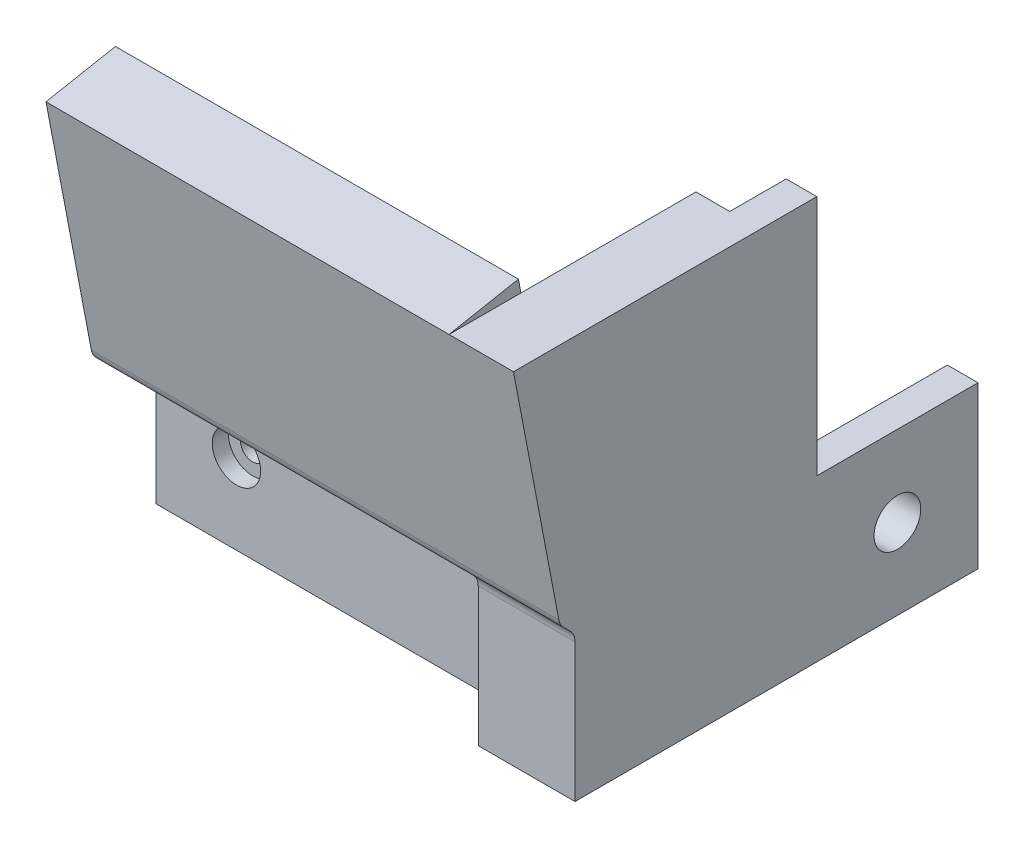
SolidWorks part; units mm, degrees
ref_plane "前视基准面" through (0, 0, 0) normal (0, 0, 1) x (1, 0, 0)
ref_plane "上视基准面" through (0, 0, 0) normal (0, 1, 0) x (1, 0, 0)
ref_plane "右视基准面" through (0, 0, 0) normal (1, 0, 0) x (0, 0, -1)
other "Configuration Table"
sketch "草图1" plane through (0, 0, 0) normal (1, 0, 0) x (0, 0, -1)
  line L0 (0, 0) -> (-10, 0)
  line L1 (-10, 0) -> (-17.6299, 40)
  line L2 (-17.6299, 40) -> (-10, 41.4554)
  line L3 (-10, 41.4554) -> (-4, 10)
  line L4 (-4, 10) -> (0, 10)
  line L5 (0, 10) -> (0, 0)
  dimension "D1" = 10
  dimension "D2" = 4
  dimension "D3" = 10
  dimension "D4" = 6
  dimension "D5" = 40
extrude "凸台-拉伸1" add sketch "草图1" along normal blind 50
sketch "草图2" plane through (0, 0, 0) normal (0, -1, 0) x (1, 0, 0)
  line L4 (0, 10) -> (0, 0)
  line L5 (0, 0) -> (50, 0)
  line L6 (50, 0) -> (50, 10)
  line L7 (50, 10) -> (0, 10)
  line L8 (0, 10) -> (0, 0)
  line L9 (0, 0) -> (50, 0)
  line L10 (50, 0) -> (50, 10)
  line L11 (50, 10) -> (0, 10)
  dimension "D1" = 0
extrude "凸台-拉伸2" add sketch "草图2" along normal blind 10
sketch "草图3" plane through (0, 0, 0) normal (-1, 0, 0) x (0, 0, 1)
  line L1 (0, 10) -> (10, 10)
  line L2 (0, 10) -> (0, -10)
  line L3 (0, -10) -> (10, -10)
  line L4 (10, 10) -> (10, -10)
extrude "凸台-拉伸3" add sketch "草图3" along normal blind 20
sketch "草图4" plane through (0, 10, 0) normal (0, 1, 0) x (1, 0, 0)
  line L1 (-20, 0) -> (0, 0)
  line L2 (-20, 0) -> (-20, -10)
  line L3 (-20, -10) -> (0, -10)
  line L4 (0, 0) -> (0, -10)
extrude "凸台-拉伸4" add sketch "草图4" along normal blind 30
sketch "草图5" plane through (50, 0, 0) normal (1, 0, 0) x (0, 0, -1)
  line L0 (-10, 10.004) -> (-11.9082, 10.004)
  line L1 (-17.6299, 40) -> (-10, 0) construction
  line L2 (-11.9082, 10.004) -> (-10, 0)
  line L3 (-10, 0) -> (-10, 10.004)
extrude "切除-拉伸1" cut sketch "草图5" against normal up to surface (50 mm away) up to face at (0, 32.2911, 11.4705)
chamfer "倒角1" distance 2 angle 45 1 edges at (25, 10.004, 10)
sketch "草图9" plane through (0, 0, 10) normal (0, 0, 1) x (1, 0, 0)
  line L0 (-20, 40) -> (-10, 40) construction
  line L1 (-20, 40) -> (0, 40) construction
  line L2 (-10, 40) -> (-10, 20) construction
  line L3 (50, -10) -> (50, 0) construction
  line L4 (50, -10) -> (50, 8.004) construction
  line L5 (50, 0) -> (10, 0) construction
  line L6 (-20, -10) -> (-20, 40) construction
  circle A0 centre (-10, 20) radius 1.5
  circle A1 centre (10, 0) radius 1.5
  dimension "D3" = 3
  dimension "D5" = 3
  dimension "D4" = 30
  dimension "D1" = 10
  dimension "D2" = 20
extrude "切除-拉伸2" cut sketch "草图9" against normal through all
sketch "草图12" plane through (0, 0, 10) normal (0, 0, 1) x (1, 0, 0)
  line L8 (0, 40) -> (-20, 40)
  line L9 (50, -10) -> (50, 8.004)
  line L10 (50, 8.004) -> (0, 8.004)
  line L11 (0, 8.004) -> (0, 40)
  line L15 (50, -10) -> (50, 8.004)
  line L16 (50, 8.004) -> (0, 8.004)
  line L17 (0, 8.004) -> (0, 40)
  line L19 (0, 40) -> (-20, 40)
  line L20 (-20, 40) -> (-20, -10)
  line L21 (-20, 40) -> (-20, -10)
  line L22 (-20, -10) -> (50, -10)
  line L23 (-20, -10) -> (50, -10)
  dimension "D1" = 0
extrude "切除-拉伸4" cut sketch "草图12" against normal blind 6
sketch "草图13" plane through (0, 8.004, 0) normal (0, -1, 0) x (1, 0, 0)
  line L0 (50, 4) -> (0, 4) construction
  line L1 (0, 10) -> (4, 10)
  line L2 (0, 10) -> (0, 4)
  line L3 (0, 4) -> (4, 4)
  line L4 (4, 10) -> (4, 4)
  line L6 (50, 10) -> (46, 10)
  line L7 (50, 10) -> (50, 4)
  line L8 (50, 4) -> (46, 4)
  line L9 (46, 10) -> (46, 4)
  dimension "D1" = 4
  dimension "D2" = 4
extrude "凸台-拉伸12" add sketch "草图13" along normal up to surface (18.004 mm away) up to face at (15, -10, 2)
fillet "圆角2" radius 2 3 edges at (25, 9.8906, 11.8866) (48, 8.004, 10) (2, 8.004, 10)
sketch "草图15" plane through (0, 0, 0) normal (0, 0, -1) x (-1, 0, 0)
  line L0 (-25, 10) -> (-25, 20.01) construction
  line L1 (0, 40) -> (20, 40) construction
  line L2 (0, 40) -> (0, -10) construction
  line L3 (0, -10) -> (20, -10) construction
  line L4 (20, 40) -> (20, -10) construction
  line L5 (-50, 10) -> (0, 10) construction
  line L6 (-50, -10) -> (-70, -10)
  line L7 (-70, 40) -> (-70, -10)
  line L8 (-50, 40) -> (-70, 40)
  line L9 (-50, 40) -> (-50, -10)
  circle A0 centre (10, 20) radius 1.5 construction
  circle A1 centre (-60, 20) radius 1.5
extrude "凸台-拉伸14" add sketch "草图15" against normal up to surface (4 mm away) up to face at (-8.5, 20, 4)
sketch "草图16" plane through (0, 0, 4) normal (0, 0, 1) x (1, 0, 0)
  line L5 (-20, -10) -> (0, -10)
  line L6 (0, -10) -> (0, 10)
  line L7 (0, 10) -> (0, 40)
  line L8 (0, 40) -> (-20, 40)
  line L9 (-20, 40) -> (-20, -10)
  line L10 (-20, -10) -> (0, -10)
  line L11 (0, -10) -> (0, 10)
  line L12 (0, 10) -> (0, 40)
  line L13 (0, 40) -> (-20, 40)
  line L14 (-20, 40) -> (-20, -10)
  dimension "D1" = 0
extrude "切除-拉伸5" cut sketch "草图16" against normal up to surface (4 mm away) up to face at (-8.5, 20, 0)
sketch "草图17" plane through (0, 0, 4) normal (0, 0, 1) x (1, 0, 0)
  line L0 (70, -10) -> (50, -10) construction
  line L1 (70, 40) -> (54, 40)
  line L2 (70, 40) -> (70, -10)
  line L3 (70, -10) -> (54, -10)
  line L4 (54, 40) -> (54, -10)
  dimension "D1" = 16
extrude "切除-拉伸6" cut sketch "草图17" against normal up to surface (4 mm away) up to face at (11.5, 0, 0)
sketch "草图18" plane through (50, 0, 0) normal (-1, 0, 0) x (0, 0, 1)
  line L0 (0, 10) -> (4, 10)
  line L1 (4, 10) -> (5.9075, 20)
  line L2 (4, 10) -> (10, 41.4554) construction
  line L3 (5.9075, 20) -> (0, 20)
  line L4 (0, 10) -> (0, 40) construction
  line L5 (0, 20) -> (0, 10)
  dimension "D1" = 10
extrude "凸台-拉伸15" add sketch "草图18" along normal blind 10
sketch "草图20" plane through (0, 0, 0) normal (0, 0, -1) x (-1, 0, 0)
  line L1 (-50, 40) -> (-54, 40)
  line L2 (-50, 40) -> (-50, -10)
  line L3 (-50, -10) -> (-54, -10)
  line L4 (-54, 40) -> (-54, -10)
extrude "凸台-拉伸16" add sketch "草图20" along normal blind 20
sketch "草图23" plane through (54, 0, 0) normal (1, 0, 0) x (0, 0, -1)
  line L0 (-4, -10) -> (-4, 20) construction
  line L1 (-4, 12) -> (20, 12)
  line L2 (-4, 12) -> (-4, -10)
  line L3 (-4, -10) -> (20, -10)
  line L4 (20, 12) -> (20, -10)
  line L5 (-5.9075, 20) -> (-4, 20) construction
  dimension "D1" = 8
extrude "切除-拉伸9" cut sketch "草图23" against normal up to surface (4 mm away) up to face at (50, 13.7188, 9.5514)
sketch "草图24" plane through (0, 0, 4) normal (0, 0, 1) x (1, 0, 0)
  line L5 (50, 12) -> (54, 12)
  line L6 (54, 12) -> (54, 40)
  line L7 (54, 40) -> (50, 40)
  line L8 (50, 40) -> (50, 20)
  line L9 (50, 20) -> (50, 12)
  line L10 (50, 12) -> (54, 12)
  line L11 (54, 12) -> (54, 40)
  line L12 (54, 40) -> (50, 40)
  line L13 (50, 40) -> (50, 20)
  line L14 (50, 20) -> (50, 12)
  dimension "D1" = 0
extrude "凸台-拉伸17" add sketch "草图24" along normal up to surface (13.6299 mm away) up to face at (25, 25.2475, 14.8159)
sketch "草图25" plane through (0, 12, 0) normal (0, -1, 0) x (1, 0, 0)
  line L1 (50, 0) -> (54, 0)
  line L2 (50, 0) -> (50, 12.289)
  line L3 (50, 12.289) -> (54, 12.289)
  line L4 (54, 0) -> (54, 12.289)
extrude "凸台-拉伸18" add sketch "草图25" along normal up to surface (22 mm away) up to face at (25, -10, 6)
sketch "草图26" plane through (50, 0, 0) normal (-1, 0, 0) x (0, 0, 1)
  line L5 (12.289, -10) -> (12.289, 12)
  line L6 (12.289, 12) -> (12.0019, 10.495)
  line L7 (11.4515, 9.4555) -> (10.5858, 8.5898)
  line L8 (10, 7.1756) -> (10, -10)
  line L9 (10, -10) -> (12.289, -10)
  line L10 (12.289, -10) -> (12.289, 12)
  line L11 (12.289, 12) -> (12.0019, 10.495)
  line L12 (11.4515, 9.4555) -> (10.5858, 8.5898)
  line L13 (10, 7.1756) -> (10, -10)
  line L14 (10, -10) -> (12.289, -10)
  arc A2 (11.4515, 9.4555) -> (12.0019, 10.495) centre (10.0373, 10.8697) ccw
  arc A3 (10.5858, 8.5898) -> (10, 7.1756) centre (12, 7.1756) ccw
  arc A4 (11.4515, 9.4555) -> (12.0019, 10.495) centre (10.0373, 10.8697) ccw
  arc A5 (10.5858, 8.5898) -> (10, 7.1756) centre (12, 7.1756) ccw
  dimension "D1" = 0
extrude "切除-拉伸10" cut sketch "草图26" against normal up to surface (4 mm away) up to face at (54, 13.7143, 0.3154)
sketch "草图27" plane through (4, 0, 0) normal (1, 0, 0) x (0, 0, -1)
  line L5 (-10, -10) -> (-4, -10)
  line L6 (-4, -10) -> (-4, 8.004)
  line L7 (-4, 8.004) -> (-10, 8.004)
  line L8 (-10, 8.004) -> (-10.5858, 8.5898)
  line L9 (-10, 7.1756) -> (-10, -10)
  line L10 (-10, -10) -> (-4, -10)
  line L11 (-4, -10) -> (-4, 8.004)
  line L12 (-4, 8.004) -> (-10, 8.004)
  line L13 (-10, 8.004) -> (-10.5858, 8.5898)
  line L14 (-10, 7.1756) -> (-10, -10)
  arc A1 (-10, 7.1756) -> (-10.5858, 8.5898) centre (-12, 7.1756) ccw
  arc A2 (-10, 7.1756) -> (-10.5858, 8.5898) centre (-12, 7.1756) ccw
  dimension "D1" = 0
extrude "切除-拉伸11" cut sketch "草图27" against normal up to surface (4 mm away) up to face at (0, 11.7188, 8.5607)
sketch "草图31" plane through (40, 0, 0) normal (-1, 0, 0) x (0, 0, 1)
  line L4 (0, 20) -> (0, 10)
  line L5 (0, 10) -> (4, 10)
  line L6 (4, 10) -> (5.9075, 20)
  line L7 (5.9075, 20) -> (0, 20)
  line L8 (0, 20) -> (0, 10)
  line L9 (0, 10) -> (4, 10)
  line L10 (4, 10) -> (5.9075, 20)
  line L11 (5.9075, 20) -> (0, 20)
  dimension "D1" = 0
extrude "切除-拉伸14" cut sketch "草图31" against normal blind 10
sketch "草图32" plane through (54, 0, 0) normal (1, 0, 0) x (0, 0, -1)
  line L8 (-10, 7.1756) -> (-10, -10)
  line L9 (-10, -10) -> (0, -10)
  line L10 (0, -10) -> (0, 12)
  line L11 (0, 12) -> (20, 12)
  line L12 (20, 12) -> (20, 40)
  line L13 (20, 40) -> (-17.6299, 40)
  line L14 (-17.6299, 40) -> (-12.0019, 10.495)
  line L15 (-11.4515, 9.4555) -> (-10.5858, 8.5898)
  line L16 (-10, 7.1756) -> (-10, -10)
  line L17 (-10, -10) -> (0, -10)
  line L18 (0, -10) -> (0, 12)
  line L19 (0, 12) -> (20, 12)
  line L20 (20, 12) -> (20, 40)
  line L21 (20, 40) -> (-17.6299, 40)
  line L22 (-17.6299, 40) -> (-12.0019, 10.495)
  line L23 (-11.4515, 9.4555) -> (-10.5858, 8.5898)
  arc A2 (-10, 7.1756) -> (-10.5858, 8.5898) centre (-12, 7.1756) ccw
  arc A3 (-12.0019, 10.495) -> (-11.4515, 9.4555) centre (-10.0373, 10.8697) ccw
  arc A4 (-10, 7.1756) -> (-10.5858, 8.5898) centre (-12, 7.1756) ccw
  arc A5 (-12.0019, 10.495) -> (-11.4515, 9.4555) centre (-10.0373, 10.8697) ccw
  dimension "D1" = 0
extrude "凸台-拉伸19" add sketch "草图32" along normal blind 4
sketch "草图35" plane through (0, 12, 0) normal (0, -1, 0) x (1, 0, 0)
  line L4 (58, 0) -> (50, 0)
  line L5 (50, 0) -> (50, -20)
  line L6 (50, -20) -> (58, -20)
  line L7 (58, -20) -> (58, 0)
  line L8 (58, 0) -> (50, 0)
  line L9 (50, 0) -> (50, -20)
  line L10 (50, -20) -> (58, -20)
  line L11 (58, -20) -> (58, 0)
  dimension "D1" = 0
extrude "凸台-拉伸20" add sketch "草图35" along normal up to surface (22 mm away) up to face at (34.6667, -10, 4.6667)
sketch "草图36" plane through (0, 0, -20) normal (0, 0, -1) x (-1, 0, 0)
  line L0 (-58, -10) -> (-58, 40) construction
  line L1 (-50, -10) -> (-58, -10)
  line L2 (-50, -10) -> (-50, 10)
  line L3 (-50, 10) -> (-58, 10)
  line L4 (-58, -10) -> (-58, 10)
  dimension "D1" = 20
extrude "凸台-拉伸21" add sketch "草图36" along normal blind 20
sketch "草图37" plane through (50, 0, 0) normal (-1, 0, 0) x (0, 0, 1)
  line L0 (-20, 40) -> (-13, 40)
  line L1 (9.7224, 40) -> (-20, 40) construction
  line L2 (-13, 40) -> (-13, 3)
  line L3 (-13, 3) -> (-40, 3)
  line L4 (-40, -10) -> (-40, 10) construction
  line L5 (-40, 3) -> (-40, 10)
  line L6 (-40, 10) -> (-20, 10)
  line L7 (-20, 10) -> (-20, 40)
  dimension "D1" = 7
  dimension "D2" = 7
extrude "切除-拉伸17" cut sketch "草图37" against normal blind 4.2
sketch "草图38" plane through (58, 0, 0) normal (1, 0, 0) x (0, 0, -1)
  line L0 (40, 0) -> (30, 0) construction
  line L1 (40, 10) -> (40, -10) construction
  circle A0 centre (30, 0) radius 1.5
  dimension "D2" = 3
  dimension "D1" = 10
extrude "切除-拉伸18" cut sketch "草图38" against normal blind 10
sketch "草图39" plane through (58, 0, 0) normal (1, 0, 0) x (0, 0, -1)
  circle A0 centre (30, 0) radius 2.9
  dimension "D1" = 5.8
extrude "切除-拉伸19" cut sketch "草图39" against normal offset from surface (6 mm away) 2 up to face at (50, 0, -28.5)
sketch "草图40" plane through (0, 0, 4) normal (0, 0, 1) x (1, 0, 0)
  circle A0 centre (10, 0) radius 3
  dimension "D1" = 6
extrude "切除-拉伸20" cut sketch "草图40" against normal offset from surface (2 mm away) 2 up to face at (11.5, 0, 0)
sketch "草图41" plane through (0, -0.3851, 2.0191) normal (0, 0.1874, -0.9823) x (-1, 0, 0)
  line L0 (0, 10.5724) -> (0, 42.5949) construction
  line L1 (0, 26.5836) -> (-50, 26.5836)
  line L2 (0, 26.5836) -> (0, 42.5949)
  line L3 (0, 42.5949) -> (-50, 42.5949)
  line L4 (-50, 26.5836) -> (-50, 42.5949)
extrude "凸台-拉伸22" add sketch "草图41" along normal blind 1
